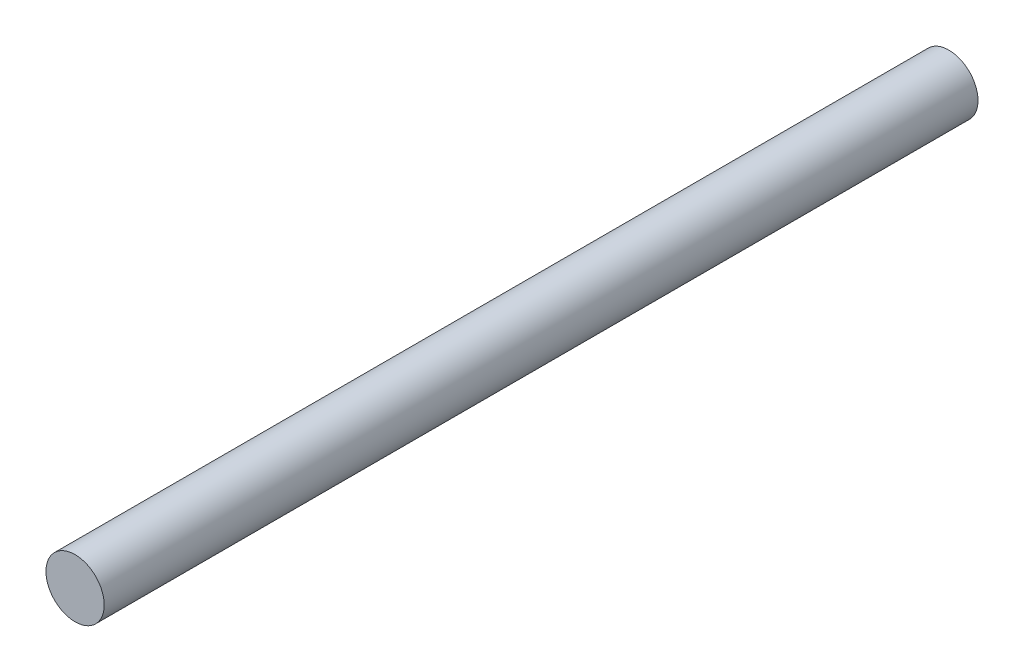
SolidWorks part; units mm, degrees
material "A286 铁基超合金"
ref_plane "前视基准面" through (0, 0, 0) normal (0, 0, 1) x (1, 0, 0)
ref_plane "上视基准面" through (0, 0, 0) normal (0, 1, 0) x (1, 0, 0)
ref_plane "右视基准面" through (0, 0, 0) normal (1, 0, 0) x (0, 0, -1)
sketch "草图3" plane through (0, 0, 0) normal (0, 0, 1) x (1, 0, 0)
  circle A0 centre (0, 0) radius 4
  dimension "D1" = 8
extrude "凸台-拉伸1" add sketch "草图3" along normal mid plane 120
